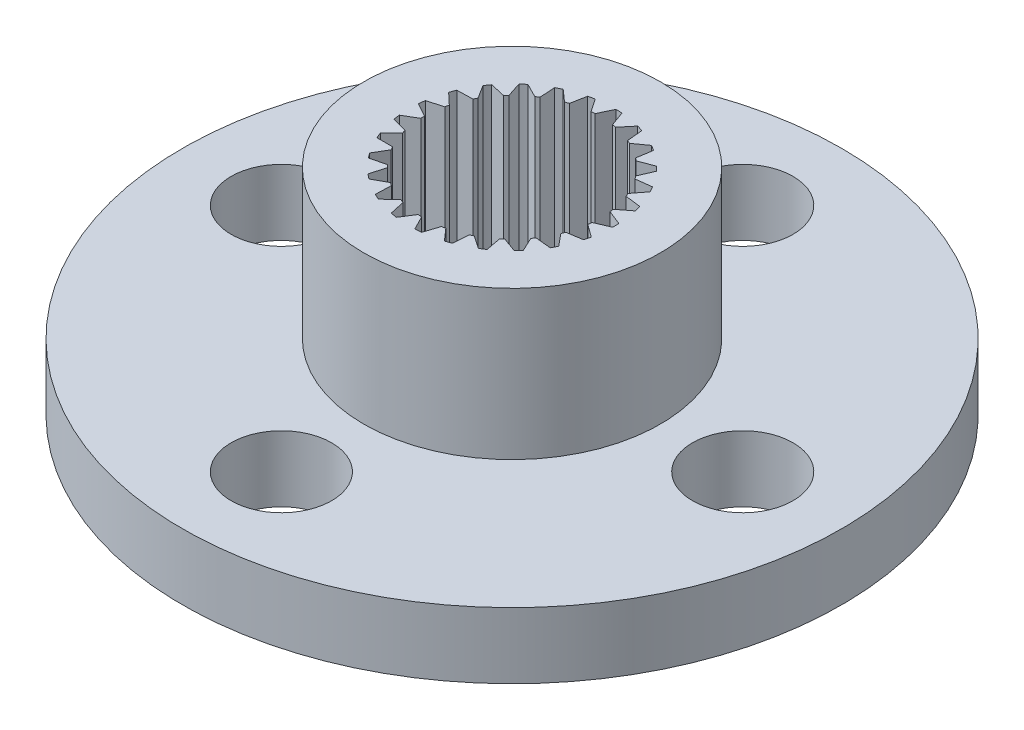
SolidWorks part; units mm, degrees
ref_plane "Front Plane" through (0, 0, 0) normal (0, 0, 1) x (1, 0, 0)
ref_plane "Top Plane" through (0, 0, 0) normal (0, 1, 0) x (1, 0, 0)
ref_plane "Right Plane" through (0, 0, 0) normal (1, 0, 0) x (0, 0, -1)
sketch "Sketch1" plane through (24.3015, 0, -59.2505) normal (0, -1, 0) x (0.9556, 0, 0.2946)
  line L0 (-1.3378, 2.3147) -> (-1.7435, 2.5633)
  line L1 (-1.8991, 2.4502) -> (-1.788, 1.9876)
  line L2 (-1.8714, 1.9093) -> (-2.3261, 2.0492)
  line L3 (-2.4487, 1.901) -> (-2.2261, 1.4805)
  line L4 (-2.2874, 1.3839) -> (-2.7627, 1.4063)
  line L5 (-2.8446, 1.2323) -> (-2.5244, 0.8804)
  line L6 (-2.5597, 0.7715) -> (-3.0256, 0.6751)
  line L7 (-3.0616, 0.4861) -> (-2.664, 0.2249)
  line L8 (-2.6712, 0.1107) -> (-3.0984, -0.0986)
  line L9 (-3.0864, -0.2905) -> (-2.6362, -0.4446)
  line L10 (-2.6148, -0.5571) -> (-2.9766, -0.866)
  line L11 (-2.9171, -1.0489) -> (-2.4428, -1.0863)
  line L12 (-2.3941, -1.1898) -> (-2.6677, -1.5791)
  line L13 (-2.5646, -1.7415) -> (-2.0959, -1.6597)
  line L14 (-2.023, -1.7478) -> (-2.1912, -2.1929)
  line L15 (-2.051, -2.3245) -> (-1.6174, -2.1288)
  line L16 (-1.5248, -2.196) -> (-1.577, -2.6689)
  line L17 (-1.4085, -2.7616) -> (-1.0371, -2.4641)
  line L18 (-0.9307, -2.5062) -> (-0.8637, -2.9772)
  line L19 (-0.6774, -3.0251) -> (-0.3918, -2.6446)
  line L20 (-0.2782, -2.659) -> (-0.0962, -3.0985)
  line L21 (0.0962, -3.0985) -> (0.2782, -2.659)
  line L22 (0.3918, -2.6446) -> (0.6774, -3.0251)
  line L23 (0.8637, -2.9772) -> (0.9307, -2.5062)
  line L24 (1.0371, -2.4641) -> (1.4085, -2.7616)
  line L25 (1.577, -2.6689) -> (1.5248, -2.196)
  line L26 (1.6174, -2.1288) -> (2.051, -2.3245)
  line L27 (2.1912, -2.1929) -> (2.023, -1.7478)
  line L28 (2.0959, -1.6597) -> (2.5646, -1.7415)
  line L29 (2.6677, -1.5791) -> (2.3941, -1.1898)
  line L30 (2.4428, -1.0863) -> (2.9171, -1.0489)
  line L31 (2.9766, -0.866) -> (2.6148, -0.5571)
  line L32 (2.6362, -0.4446) -> (3.0864, -0.2905)
  line L33 (3.0984, -0.0986) -> (2.6712, 0.1107)
  line L34 (2.664, 0.2249) -> (3.0616, 0.4861)
  line L35 (3.0256, 0.6751) -> (2.5597, 0.7715)
  line L36 (2.5244, 0.8804) -> (2.8446, 1.2323)
  line L37 (2.7627, 1.4063) -> (2.2874, 1.3839)
  line L38 (2.2261, 1.4805) -> (2.4487, 1.901)
  line L39 (2.3261, 2.0492) -> (1.8714, 1.9093)
  line L40 (1.788, 1.9876) -> (1.8991, 2.4502)
  line L41 (1.7435, 2.5633) -> (1.3378, 2.3147)
  line L42 (1.2375, 2.3698) -> (1.23, 2.8455)
  line L43 (1.0512, 2.9163) -> (0.7201, 2.5747)
  line L44 (0.6093, 2.6031) -> (0.4837, 3.062)
  line L45 (0.2929, 3.0861) -> (0.0572, 2.6729)
  line L46 (-0.0572, 2.6729) -> (-0.2929, 3.0861)
  line L47 (-0.4837, 3.062) -> (-0.6093, 2.6031)
  line L48 (-0.7201, 2.5747) -> (-1.0512, 2.9163)
  line L49 (-1.23, 2.8455) -> (-1.2375, 2.3698)
  line L200 (-1.8428, 2.4303) -> (-1.7394, 1.9993) construction
  line L201 (-1.3639, 2.272) -> (-1.7419, 2.5037) construction
  line L202 (-1.8861, 1.8615) -> (-2.3098, 1.9918) construction
  line L203 (-2.3893, 1.8957) -> (-2.1819, 1.5039) construction
  line L204 (-2.2898, 1.3339) -> (-2.7326, 1.3548) construction
  line L205 (-2.7857, 1.2419) -> (-2.4874, 0.914) construction
  line L206 (-3.007, 0.5101) -> (-2.6365, 0.2667) construction
  line L207 (-2.5496, 0.7226) -> (-2.9837, 0.6327) construction
  line L208 (-3.0394, -0.2537) -> (-2.62, -0.3973) construction
  line L209 (-2.6492, 0.0658) -> (-3.0473, -0.1292) construction
  line L210 (-2.8808, -1.0016) -> (-2.4389, -1.0364) construction
  line L211 (-2.5823, -0.5951) -> (-2.9194, -0.883) construction
  line L212 (-2.5412, -1.6866) -> (-2.1045, -1.6104) construction
  line L213 (-2.3532, -1.2186) -> (-2.6081, -1.5812) construction
  line L214 (-2.0419, -2.2656) -> (-1.6379, -2.0832) construction
  line L215 (-1.9762, -1.7655) -> (-2.1329, -2.1802) construction
  line L216 (-1.4144, -2.7022) -> (-1.0684, -2.4251) construction
  line L217 (-1.4751, -2.2015) -> (-1.5237, -2.6421) construction
  line L218 (-0.6979, -2.9691) -> (-0.4318, -2.6146) construction
  line L219 (-0.8812, -2.4992) -> (-0.8188, -2.938) construction
  line L220 (0.0624, -3.0494) -> (0.232, -2.6398) construction
  line L221 (-0.232, -2.6398) -> (-0.0624, -3.0494) construction
  line L222 (0.8188, -2.938) -> (0.8812, -2.4992) construction
  line L223 (0.4318, -2.6146) -> (0.6979, -2.9691) construction
  line L224 (1.0684, -2.4251) -> (1.4144, -2.7022) construction
  line L225 (1.5237, -2.6421) -> (1.4751, -2.2015) construction
  line L226 (1.6379, -2.0832) -> (2.0419, -2.2656) construction
  line L227 (2.1329, -2.1802) -> (1.9762, -1.7655) construction
  line L228 (2.1045, -1.6104) -> (2.5412, -1.6866) construction
  line L229 (2.6081, -1.5812) -> (2.3532, -1.2186) construction
  line L230 (2.4389, -1.0364) -> (2.8808, -1.0016) construction
  line L231 (2.9194, -0.883) -> (2.5823, -0.5951) construction
  line L232 (3.0473, -0.1292) -> (2.6492, 0.0658) construction
  line L233 (2.62, -0.3973) -> (3.0394, -0.2537) construction
  line L234 (2.9837, 0.6327) -> (2.5496, 0.7226) construction
  line L235 (2.6365, 0.2667) -> (3.007, 0.5101) construction
  line L236 (2.7326, 1.3548) -> (2.2898, 1.3339) construction
  line L237 (2.4874, 0.914) -> (2.7857, 1.2419) construction
  line L238 (2.3098, 1.9918) -> (1.8861, 1.8615) construction
  line L239 (2.1819, 1.5039) -> (2.3893, 1.8957) construction
  line L240 (1.7394, 1.9993) -> (1.8428, 2.4303) construction
  line L241 (1.7419, 2.5037) -> (1.3639, 2.272) construction
  line L242 (1.0645, 2.8582) -> (0.756, 2.5399) construction
  line L243 (1.1875, 2.369) -> (1.1806, 2.8123) construction
  line L244 (0.5611, 2.5899) -> (0.4441, 3.0175) construction
  line L245 (0.3203, 3.0331) -> (0.1007, 2.6481) construction
  line L246 (-0.4441, 3.0175) -> (-0.5611, 2.5899) construction
  line L247 (-0.1007, 2.6481) -> (-0.3203, 3.0331) construction
  line L248 (-1.1806, 2.8123) -> (-1.1875, 2.369) construction
  line L249 (-0.756, 2.5399) -> (-1.0645, 2.8582) construction
  arc A0 (-1.7435, 2.5633) -> (-1.8991, 2.4502) centre (0, 0) ccw
  arc A1 (-2.3261, 2.0492) -> (-2.4487, 1.901) centre (0, 0) ccw
  arc A2 (-2.7627, 1.4063) -> (-2.8446, 1.2323) centre (0, 0) ccw
  arc A3 (-3.0256, 0.6751) -> (-3.0616, 0.4861) centre (0, 0) ccw
  arc A4 (-3.0984, -0.0986) -> (-3.0864, -0.2905) centre (0, 0) ccw
  arc A5 (-2.9766, -0.866) -> (-2.9171, -1.0489) centre (0, 0) ccw
  arc A6 (-2.6677, -1.5791) -> (-2.5646, -1.7415) centre (0, 0) ccw
  arc A7 (-2.1912, -2.1929) -> (-2.051, -2.3245) centre (0, 0) ccw
  arc A8 (-1.577, -2.6689) -> (-1.4085, -2.7616) centre (0, 0) ccw
  arc A9 (-0.8637, -2.9772) -> (-0.6774, -3.0251) centre (0, 0) ccw
  arc A10 (-0.0962, -3.0985) -> (0.0962, -3.0985) centre (0, 0) ccw
  arc A11 (0.6774, -3.0251) -> (0.8637, -2.9772) centre (0, 0) ccw
  arc A12 (1.4085, -2.7616) -> (1.577, -2.6689) centre (0, 0) ccw
  arc A13 (2.051, -2.3245) -> (2.1912, -2.1929) centre (0, 0) ccw
  arc A14 (2.5646, -1.7415) -> (2.6677, -1.5791) centre (0, 0) ccw
  arc A15 (2.9171, -1.0489) -> (2.9766, -0.866) centre (0, 0) ccw
  arc A16 (3.0864, -0.2905) -> (3.0984, -0.0986) centre (0, 0) ccw
  arc A17 (3.0616, 0.4861) -> (3.0256, 0.6751) centre (0, 0) ccw
  arc A18 (2.8446, 1.2323) -> (2.7627, 1.4063) centre (0, 0) ccw
  arc A19 (2.4487, 1.901) -> (2.3261, 2.0492) centre (0, 0) ccw
  arc A20 (1.8991, 2.4502) -> (1.7435, 2.5633) centre (0, 0) ccw
  arc A21 (1.23, 2.8455) -> (1.0512, 2.9163) centre (0, 0) ccw
  arc A22 (0.4837, 3.062) -> (0.2929, 3.0861) centre (0, 0) ccw
  arc A23 (-0.2929, 3.0861) -> (-0.4837, 3.062) centre (0, 0) ccw
  arc A24 (-1.0512, 2.9163) -> (-1.23, 2.8455) centre (0, 0) ccw
  circle A25 centre (0, 0) radius 2.6735
  circle A152 centre (0, 0) radius 4.5
  arc A205 (-1.7419, 2.5037) -> (-1.8428, 2.4303) centre (0, 0) ccw construction
  arc A206 (-2.3098, 1.9918) -> (-2.3893, 1.8957) centre (0, 0) ccw construction
  arc A208 (-2.7326, 1.3548) -> (-2.7857, 1.2419) centre (0, 0) ccw construction
  arc A211 (-2.9837, 0.6327) -> (-3.007, 0.5101) centre (0, 0) ccw construction
  arc A213 (-3.0473, -0.1292) -> (-3.0394, -0.2537) centre (0, 0) ccw construction
  arc A215 (-2.9194, -0.883) -> (-2.8808, -1.0016) centre (0, 0) ccw construction
  arc A217 (-2.6081, -1.5812) -> (-2.5412, -1.6866) centre (0, 0) ccw construction
  arc A219 (-2.1329, -2.1802) -> (-2.0419, -2.2656) centre (0, 0) ccw construction
  arc A221 (-1.5237, -2.6421) -> (-1.4144, -2.7022) centre (0, 0) ccw construction
  arc A223 (-0.8188, -2.938) -> (-0.6979, -2.9691) centre (0, 0) ccw construction
  arc A225 (-0.0624, -3.0494) -> (0.0624, -3.0494) centre (0, 0) ccw construction
  arc A227 (0.6979, -2.9691) -> (0.8188, -2.938) centre (0, 0) ccw construction
  arc A228 (1.4144, -2.7022) -> (1.5237, -2.6421) centre (0, 0) ccw construction
  arc A230 (2.0419, -2.2656) -> (2.1329, -2.1802) centre (0, 0) ccw construction
  arc A232 (2.5412, -1.6866) -> (2.6081, -1.5812) centre (0, 0) ccw construction
  arc A234 (2.8808, -1.0016) -> (2.9194, -0.883) centre (0, 0) ccw construction
  arc A237 (3.0394, -0.2537) -> (3.0473, -0.1292) centre (0, 0) ccw construction
  arc A239 (3.007, 0.5101) -> (2.9837, 0.6327) centre (0, 0) ccw construction
  arc A241 (2.7857, 1.2419) -> (2.7326, 1.3548) centre (0, 0) ccw construction
  arc A243 (2.3893, 1.8957) -> (2.3098, 1.9918) centre (0, 0) ccw construction
  arc A244 (1.8428, 2.4303) -> (1.7419, 2.5037) centre (0, 0) ccw construction
  arc A247 (1.1806, 2.8123) -> (1.0645, 2.8582) centre (0, 0) ccw construction
  arc A248 (0.4441, 3.0175) -> (0.3203, 3.0331) centre (0, 0) ccw construction
  arc A251 (-0.3203, 3.0331) -> (-0.4441, 3.0175) centre (0, 0) ccw construction
  arc A253 (-1.0645, 2.8582) -> (-1.1806, 2.8123) centre (0, 0) ccw construction
  dimension "D2" = 9
  dimension "D1" = 0.05
extrude "Boss-Extrude1" add sketch "Sketch1" against normal blind 6.5 contours A152 L43 A25 L44 A22 L45 L46 A23 L47 L48 A24 L49 L0 A0 L1 L2 A1 L3 L4 A2 L5 L6 A3 L7 L8 A4 L9 L10 A5 L11 L12 A6 L13 L14 A7 L15 L16 A8 L17 region at (20.1228, 0, -60.5386)
sketch "Sketch2" plane through (0, 0, 0) normal (0, -1, 0) x (-1, 0, 0)
  circle A0 centre (-24.3015, 59.2505) radius 10
  dimension "D1" = 20
extrude "Boss-Extrude2" add sketch "Sketch2" against normal blind 2
sketch "Sketch3" plane through (0, 0, 0) normal (0, -1, 0) x (-1, 0, 0)
  circle A6 centre (-24.3015, 66.2505) radius 1.525
  circle A8 centre (-17.3015, 59.2505) radius 1.525
  circle A9 centre (-24.3015, 52.2505) radius 1.525
  circle A10 centre (-31.3015, 59.2505) radius 1.525
  circle A13 centre (-24.3015, 59.2505) radius 10
  circle A14 centre (-24.3015, 59.2505) radius 10 construction
  point P17 (-24.3015, 59.2505)
  dimension "D1" = 3.05
  dimension "D4" = 14
  dimension "D2" = 4
  dimension "D3" = 0
  dimension "D5" = 7
extrude "Cut-Extrude1" cut sketch "Sketch3" against normal through all
